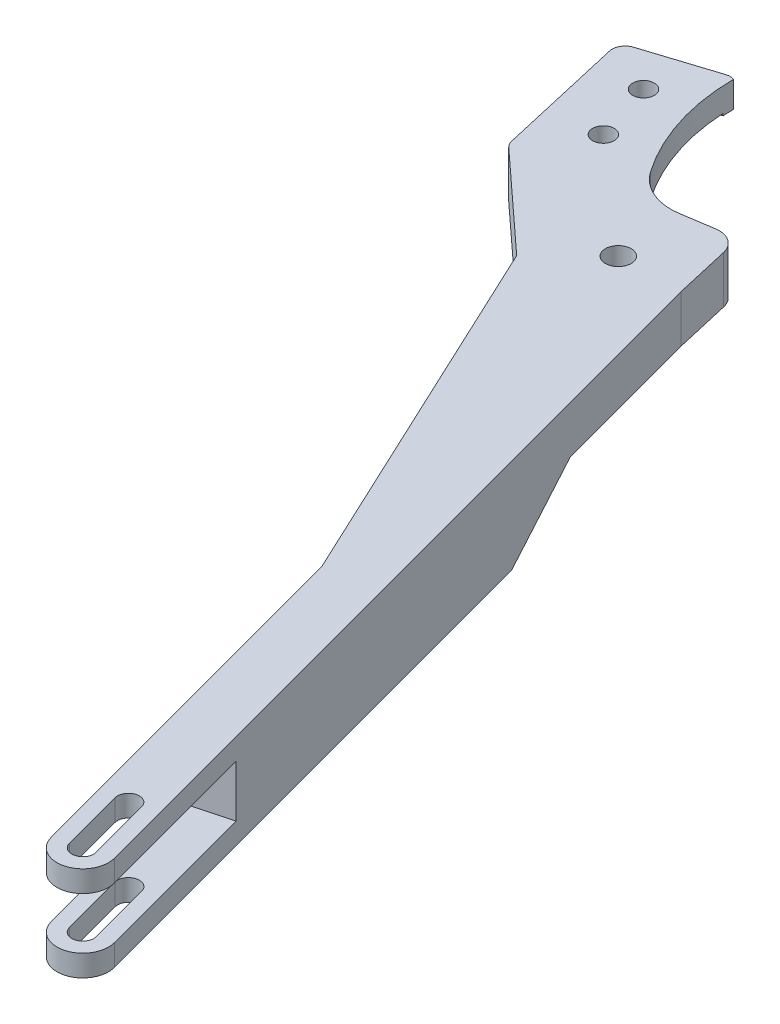
SolidWorks part; units mm, degrees
material "6061-T6 (SS)"
ref_plane "Front Plane" through (0, 0, 0) normal (0, 0, 1) x (1, 0, 0)
ref_plane "Top Plane" through (0, 0, 0) normal (0, 1, 0) x (1, 0, 0)
ref_plane "Right Plane" through (0, 0, 0) normal (1, 0, 0) x (0, 0, -1)
sketch "Sketch1" plane through (0, 0, 0) normal (0, 1, 0) x (1, 0, 0)
  line L9 (14.4784, 0.0716) -> (63.2363, -181.8954)
  line L10 (63.2363, -181.8954) -> (51.6452, -185.0012)
  line L11 (51.6452, -185.0012) -> (4.5666, -9.3015)
  line L13 (56.9231, -181.5164) -> (53.0409, -167.0276) construction
  line L39 (-32.9192, 36.0221) -> (-28.4593, 22.225)
  line L42 (-35.5547, 10.7127) -> (-42.3465, 40.3354)
  line L45 (-40.3375, 43.8628) -> (-24.0659, 49.0744)
  line L46 (-20.7333, 47.9937) -> (14.4784, 0.0716)
  line L47 (5.8862, 16.8196) -> (-8.2379, 14.6599)
  line L49 (-34.6601, 9.1739) -> (10.808, -32.5945)
  line L50 (54.46, -182.1764) -> (50.5777, -167.6876)
  line L51 (59.3863, -180.8565) -> (55.504, -166.3676)
  line L52 (14.4784, 0.0716) -> (11.5155, 12.9944)
  line L53 (-37.544, 31.679) -> (-40.2211, 31.0652)
  line L54 (-40.3375, 43.8628) -> (-37.544, 31.679)
  line L55 (-40.2211, 31.0652) -> (-37.544, 31.679)
  line L56 (-37.544, 31.679) -> (-35.0162, 32.2585)
  line L57 (-40.2211, 31.0652) -> (-23.4809, 34.9033)
  line L58 (-30.6912, 36.5588) -> (-26.2313, 22.7618)
  line L59 (-11.9261, -11.7103) -> (28.1059, -97.1513)
  circle A0 centre (0, 0) radius 3
  circle A1 centre (57.4408, -183.4483) radius 6
  circle A7 centre (-32.9192, 36.0221) radius 3.2247
  circle A8 centre (-28.4593, 22.225) radius 3.2247
  arc A12 (-24.0659, 49.0744) -> (-20.7333, 47.9937) centre (-23.1508, 46.2173) cw
  circle A15 centre (27.7755, 49.3447) radius 50
  arc A16 (-34.6601, 9.1739) -> (-35.5547, 10.7127) centre (-32.6306, 11.3832) cw
  arc A17 (-42.3465, 40.3354) -> (-40.3375, 43.8628) centre (-39.4224, 41.0058) cw
  circle A18 centre (56.9231, -181.5164) radius 6
  arc A19 (54.46, -182.1764) -> (59.3863, -180.8565) centre (56.9231, -181.5164) ccw
  arc A20 (55.504, -166.3676) -> (50.5777, -167.6876) centre (53.0409, -167.0276) ccw
  circle A21 centre (-3.333, 27.5883) radius 12.0384
  arc A22 (11.5155, 12.9944) -> (5.8862, 16.8196) centre (6.642, 11.877) ccw
  circle A23 centre (-30.6912, 36.5588) radius 2.5
  circle A24 centre (-26.2313, 22.7618) radius 2.5
  circle A25 centre (-28.7894, -24.0826) radius 20.5195
  point P17 (54.982, -174.272)
  point P26 (-22.0109, 49.7326)
  point P36 (-35.3465, 9.8044)
  point P39 (-42.9625, 43.0221)
  dimension "D7" = 6
  dimension "D19" = 12
  dimension "D20" = 12
  dimension "D17" = 49.3447
  dimension "D23" = 5
  dimension "D24" = 8.225
  dimension "D26" = 22
  dimension "D25" = 7
  dimension "D28" = 3
  dimension "D14" = 22.225
  dimension "D5" = 6.4493
  dimension "D8" = 6.4493
  dimension "D15" = 5.2116
  dimension "D31" = 14.1242
  dimension "D34" = 3
  dimension "D35" = 3
  dimension "D38" = 2.55
  dimension "D16" = 100
  dimension "D39" = 27.5883
  dimension "D40" = 5
  dimension "D41" = 5
  dimension "D50" = 5
  dimension "D51" = 41.0391
  dimension "D30" = 24.0769
  dimension "D3" = 175.6998
  dimension "D4" = 47.0786
  dimension "D6" = 192.2309
  dimension "D9" = 2.913
  dimension "D10" = 14.5
  dimension "D11" = 90
  dimension "D12" = 12
  dimension "D13" = 28.4593
  dimension "D18" = 183.4483
  dimension "D21" = 6
  dimension "D22" = 2
  dimension "D27" = 61.6253
  dimension "D29" = 27.7755
  dimension "D32" = 42.3989
  dimension "D33" = 62.673
  dimension "D36" = 6
  dimension "D37" = 15
  dimension "D42" = 11
  dimension "D43" = 0
  dimension "D44" = 12.5
  dimension "D45" = 5.34
  dimension "D46" = 3.225
  dimension "D47" = 17.1746
  dimension "D48" = 0
  dimension "D49" = 14.5
extrude "Boss-Extrude1" add sketch "Sketch1" along normal blind 11 contours A24 A8 L39 A7 L53 L42 A16 L49 L11 A18 L50 A20 L51 L9 L46 A15 A12 L45 L54 A23 L58 A0 | A23 A7 L57 L39 | A23 L39 L57 A7 | A23 A7 L57 L58 | A24 L58 L57 A7 L39 A8 | A17 L42 L53 L54 | A24 A8 L39 | A24 L39 A8 | L47 A15 L46 | L52 A22 L47 L46 A15 | A21 A15 L47 | L49 L59 L11 | A1 A18 L51 | L50 A18 A1 | A19 L10 A18 | A19 L10 A18 A1 L51 | A19 L50 A1 A18 L10 | A15 L46 L52 region at (-34.083, 0, -35.9681) region at (36.1439, 0, 90.6037) region at (14.0579, 0, -0.9067) region at (60.2808, 0, 177.5836) region at (2.5202, 0, -10.0094) region at (9.1036, 0, -11.0198) region at (60.6414, 0, 180.4187) region at (-7.9723, 0, -16.0887) region at (57.8835, 0, 185.1004) region at (52.0489, 0, 179.7893) region at (53.1542, 0, 182.4249) region at (8.9959, 0, 47.1521) region at (-40.1653, 0, -37.1545) region at (-31.5806, 0, -33.7994) region at (-29.5263, 0, -29.294) region at (-30.4042, 0, -33.6001) region at (-28.501, 0, -24.7075) region at (-29.5408, 0, -21.6352)
sketch "Sketch15" plane through (0, 0, 0) normal (0, -1, 0) x (1, 0, 0)
  line L0 (56.9231, 181.5164) -> (53.0409, 167.0276) construction
  line L1 (59.3969, 180.8536) -> (55.5146, 166.3647)
  line L2 (54.4494, 182.1793) -> (50.5671, 167.6904)
  line L3 (12.3047, 38.1805) -> (23.8958, 35.0747)
  line L5 (14.4784, -0.0716) -> (62.7187, 179.9635) construction
  line L6 (51.1276, 183.0694) -> (28.1059, 97.1513) construction
  line L7 (12.3047, 38.1805) -> (51.1276, 183.0694)
  line L8 (23.8958, 35.0747) -> (62.7187, 179.9635)
  circle A0 centre (56.9231, 181.5164) radius 6
  arc A1 (59.3969, 180.8536) -> (54.4494, 182.1793) centre (56.9231, 181.5164) ccw
  arc A2 (50.5671, 167.6904) -> (55.5146, 166.3647) centre (53.0409, 167.0276) ccw
  point P3 (54.982, 174.272)
  arc M13 (62.7187, 179.9635) -> (51.1276, 183.0694) centre (56.9231, 181.5164) ccw
  line M14 (51.1276, 183.0694) -> (28.1059, 97.1513)
  line M40 (14.4784, -0.0716) -> (62.7187, 179.9635)
  dimension "D1" = 12
  dimension "D2" = 2.5611
  dimension "D3" = 150
extrude "Boss-Extrude2" add sketch "Sketch15" along normal blind 11 contours A2 L2 A0 L7 L3 L1 M14 M40 | A1 L1 A0 L2 M13 region at (57.6297, 0, 184.1535) region at (36.323, 0, 104.6357)
sketch "Sketch17" plane through (0, 0, 0) normal (0, -1, 0) x (1, 0, 0)
  line L2 (6.8134, -16.8741) -> (-22.0519, -50.7351)
  line L3 (-22.0519, -50.7351) -> (-38.9832, -44.2966)
  line L4 (-40.3375, -43.8628) -> (-24.0659, -49.0744) construction
  line L6 (-38.9832, -44.2966) -> (-29.8516, -16.0472)
  line L7 (-2.1851, -12.6209) -> (-22.7132, -11.2166)
  line L8 (7.4405, -16.8129) -> (7.1642, -17.4789)
  line L9 (-1.1626, -11.1372) -> (8.237, -11.7802)
  line L10 (7.1642, -17.4789) -> (6.8134, -16.8741)
  line L13 (-29.8516, -16.0472) -> (-29.3758, -16.201)
  line L14 (-29.3758, -16.201) -> (-38.9832, -44.2966)
  line L17 (-22.5604, -11.813) -> (-3.0319, -13.1489)
  line L19 (-38.9832, -44.2966) -> (-29.4922, -16.5413)
  line L21 (-3.4066, -13.424) -> (-22.4922, -12.1184)
  line L22 (-38.9832, -44.2966) -> (-29.5934, -16.8371)
  line L23 (4.9999, -11.5587) -> (7.4405, -16.8129)
  line L24 (-2.1851, -12.6209) -> (-1.8851, -12.6209)
  arc A1 (5.8862, -16.8196) -> (11.5155, -12.9944) centre (6.642, -11.877) ccw construction
  circle A2 centre (2.4985, -21.0751) radius 9.6649
  arc A3 (-22.7132, -11.2166) -> (-29.8516, -16.0472) centre (-23.191, -18.2002) ccw
  circle A5 centre (-22.0687, -19.1643) radius 7.8852
  arc A6 (-29.4922, -16.5413) -> (-22.5604, -11.813) centre (-22.8688, -18.8062) cw
  arc A7 (-22.4922, -12.1184) -> (-29.5934, -16.8371) centre (-22.9699, -19.102) ccw
  point P22 (-28.1695, -10.8433)
  point P48 (5.0961, -11.7658)
  line M9 (-40.3375, -43.8628) -> (-24.0659, -49.0744)
  arc M10 (-24.0659, -49.0744) -> (-22.2238, -49.0705) centre (-23.1508, -46.2173) ccw
  arc M11 (-22.2238, -49.0705) -> (-13.1982, -20.6888) centre (27.7755, -49.3447) cw
  arc M17 (-32.5944, -32.8138) -> (-31.8138, -32.9928) centre (-32.9192, -36.0221) cw
  line M19 (-1.5134, -15.6881) -> (5.8862, -16.8196)
  arc M21 (-13.1982, -20.6888) -> (-1.5134, -15.6881) centre (-3.333, -27.5883) cw
  arc M22 (5.8862, -16.8196) -> (11.5155, -12.9944) centre (6.642, -11.877) ccw
  circle M49 centre (-26.2313, -22.7618) radius 2.5
  line M55 (-31.8138, -32.9928) -> (-32.5944, -32.8138)
  circle M62 centre (-30.6912, -36.5588) radius 2.5
  dimension "D7" = 19.3298
  dimension "D8" = 7
  dimension "D19" = 15.7704
  dimension "D23" = 7
  dimension "D30" = 7
  dimension "D1" = 25.9844
  dimension "D2" = 267.093
  dimension "D3" = 16.9313
  dimension "D4" = 44.4946
  dimension "D5" = 8.4542
  dimension "D6" = 4.6836
  dimension "D9" = 1.55
  dimension "D10" = 1.0224
  dimension "D11" = 9.3996
  dimension "D12" = 0.7211
  dimension "D13" = 5.7933
  dimension "D14" = 5.0327
  dimension "D15" = 0.6992
  dimension "D16" = 0.643
  dimension "D17" = 12.6209
  dimension "D18" = 0.5
  dimension "D20" = 2.1851
  dimension "D21" = 38.9832
  dimension "D22" = 180
  dimension "D24" = 19.5285
  dimension "D25" = 20.3753
  dimension "D28" = 180
  dimension "D29" = 0.3
  dimension "D34" = 0.3
  dimension "D35" = 0.2
extrude "Cut-Extrude8" cut sketch "Sketch17" against normal blind 5.42 contours L23 A2 M21 M19 M22 | A2 L2 M21 M22 M19 | A5 L22 A2 L21 M9 M10 M11 M21 M49 M62 M55 M17 | L21 A7 L19 A5 M49 region at (-1.7831, 0, -20.7936) region at (1.6278, 0, -14.1662) region at (-25.5508, 0, -33.216) region at (-21.5584, 0, -19.0078)
sketch "Sketch19" plane through (13.5265, 0, -3.6244) normal (0.9659, 0, -0.2588) x (-0.2588, 0, -0.9659)
  line L0 (-59.3696, -11) -> (-40.0642, 0)
  line L2 (-40.0642, 0) -> (-40.0642, -11)
  line L3 (-40.0642, -11) -> (-59.3696, -11)
  dimension "D1" = 19.3054
  dimension "D2" = 130.6946
extrude "Cut-Extrude9" cut sketch "Sketch19" against normal through all
sketch "Sketch22" plane through (0, 5.42, 0) normal (0, -1, 0) x (1, 0, 0)
  line L1 (-33.1, -33.3189) -> (-31.4078, -33.3189)
  line L2 (-33.1, -33.3189) -> (-33.1, -32.3189)
  line L3 (-33.1, -32.3189) -> (-31.4078, -32.3189)
  line L4 (-31.4078, -33.3189) -> (-31.4078, -32.3189)
  dimension "D1" = 1.6922
  dimension "D2" = 1
  dimension "D3" = 32.3189
  dimension "D4" = 31.4078
extrude "Boss-Extrude5" add sketch "Sketch22" against normal through all
sketch "Sketch23" plane through (0, 5.42, 0) normal (0, -1, 0) x (1, 0, 0)
  line L0 (-38.0125, -41.4579) -> (-22.1458, -46.5398)
  line L1 (-29.5934, -16.8371) -> (-38.9832, -44.2966) construction
  line L2 (-38.9832, -44.2966) -> (-24.0659, -49.0744) construction
  line L3 (-38.0125, -41.4579) -> (-38.9832, -44.2966)
  line L4 (-24.0659, -49.0744) -> (-38.9832, -44.2966)
  arc A0 (-13.1982, -20.6888) -> (-22.2238, -49.0705) centre (27.7755, -49.3447) ccw construction
  circle A1 centre (27.7755, -49.3447) radius 50
  circle A3 centre (-23.1508, -46.2173) radius 3
  line M9 (-29.5934, -16.8371) -> (-38.9832, -44.2966)
  line M10 (-38.9832, -44.2966) -> (-24.0659, -49.0744)
  arc M11 (-24.0659, -49.0744) -> (-22.2238, -49.0705) centre (-23.1508, -46.2173) ccw
  arc M12 (-22.2238, -49.0705) -> (-13.1982, -20.6888) centre (27.7755, -49.3447) cw
  dimension "D7" = 6
  dimension "D1" = 180
  dimension "D2" = 3
  dimension "D3" = 49.3447
  dimension "D4" = 27.7755
  dimension "D5" = 1.005
  dimension "D6" = 1.0555
extrude "Boss-Extrude6" add sketch "Sketch23" along normal blind 0.5 contours A3 L0 M9 M10 | L0 A3 M11 M12 region at (-32.1716, 5.42, -44.9469) region at (-24.0941, 5.42, -47.3554)
sketch "Sketch26" plane through (0, -11, 0) normal (0, -1, 0) x (1, 0, 0)
  line L0 (51.1276, 183.0694) -> (40.7748, 144.4323)
  line L1 (51.1276, 183.0694) -> (17.3013, 56.8281) construction
  line L2 (40.7748, 144.4323) -> (52.3659, 141.3265)
  line L3 (28.8925, 53.7223) -> (62.7187, 179.9635) construction
  line L4 (52.3659, 141.3265) -> (62.7187, 179.9635)
  circle A0 centre (56.9231, 181.5164) radius 6
  line M3 (28.8925, 53.7223) -> (62.7187, 179.9635)
  arc M4 (62.7187, 179.9635) -> (51.1276, 183.0694) centre (56.9231, 181.5164) ccw
  line M5 (51.1276, 183.0694) -> (17.3013, 56.8281)
  line M6 (50.5671, 167.6904) -> (54.4494, 182.1793)
  arc M7 (54.4494, 182.1793) -> (59.3969, 180.8536) centre (56.9231, 181.5164) cw
  line M8 (59.3969, 180.8536) -> (55.5146, 166.3647)
  arc M9 (55.5146, 166.3647) -> (50.5671, 167.6904) centre (53.0409, 167.0276) cw
  dimension "D1" = 40
extrude "Cut-Extrude11" cut sketch "Sketch26" against normal blind 12 from offset 5 contours A0 L2 M8 M9 M6 M5 M3 | A0 | A0 | A0 M8 M4 M6 M7 region at (50.7012, -11, 158.296) region at (57.6842, -11, 187.2975) region at (56.4362, -11, 179.6991) region at (53.9661, -11, 170.4805) offset against normal yes
sketch "Sketch27" plane through (0, -11, 0) normal (0, -1, 0) x (1, 0, 0)
  line L0 (12.3047, 38.1805) -> (16.187, 52.6694)
  line L1 (17.3013, 56.8281) -> (12.3047, 38.1805) construction
  line L2 (16.187, 52.6694) -> (16.1684, 37.1452)
  line L3 (12.3047, 38.1805) -> (23.8958, 35.0747) construction
  line L4 (16.1684, 37.1452) -> (12.3047, 38.1805)
  dimension "D1" = 4
  dimension "D2" = 15
extrude "Cut-Extrude12" cut sketch "Sketch27" against normal blind 11
equation "\"weightkg\"= \"SW-Mass\" / 1000"
